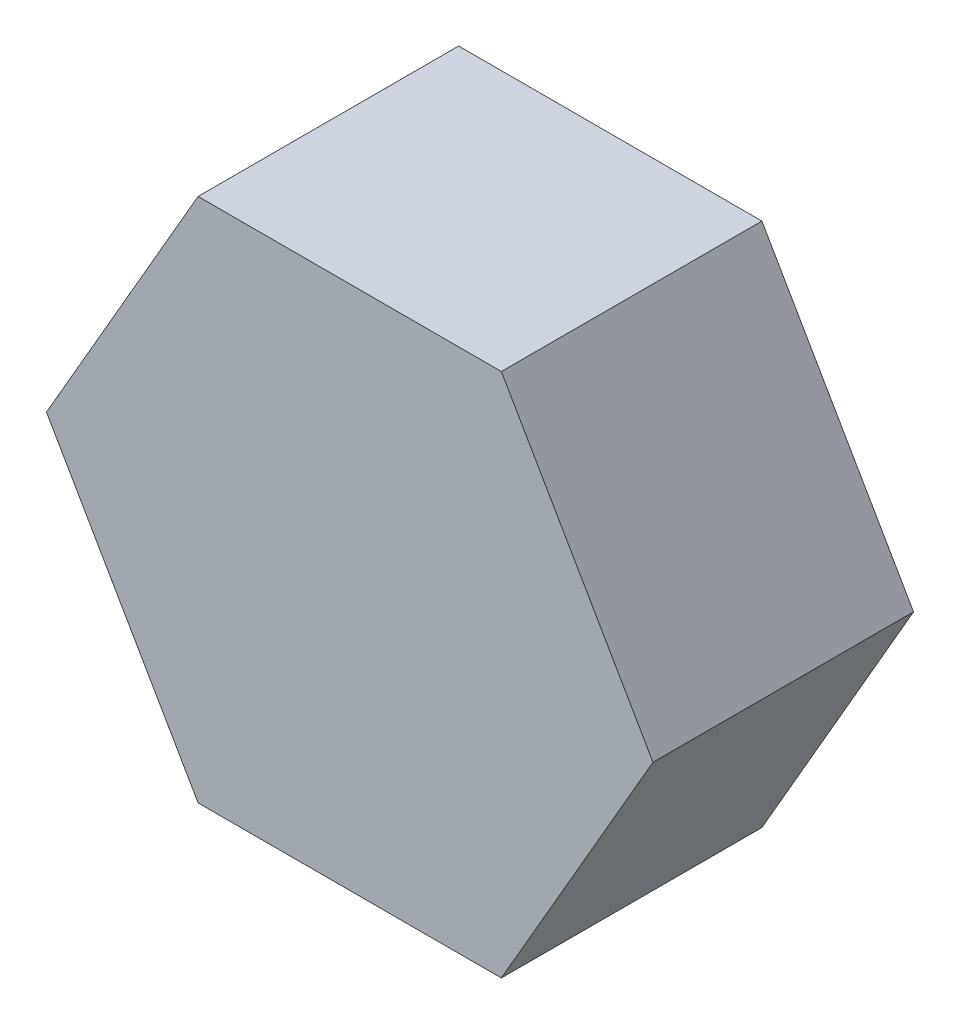
SolidWorks part; units mm, degrees
material "AISI 1020"
ref_plane "Front Plane" through (0, 0, 0) normal (0, 0, 1) x (1, 0, 0)
ref_plane "Top Plane" through (0, 0, 0) normal (0, 1, 0) x (1, 0, 0)
ref_plane "Right Plane" through (0, 0, 0) normal (1, 0, 0) x (0, 0, -1)
sketch "Sketch1" plane through (0, 0, 0) normal (0, 0, 1) x (1, 0, 0)
  line L7 (-14.5492, 25.2) -> (-29.0985, 0)
  line L8 (-29.0985, 0) -> (-14.5492, -25.2)
  line L9 (-14.5492, -25.2) -> (14.5492, -25.2)
  line L10 (14.5492, -25.2) -> (29.0985, 0)
  line L11 (29.0985, 0) -> (14.5492, 25.2)
  line L12 (14.5492, 25.2) -> (-14.5492, 25.2)
  circle A0 centre (0, 0) radius 25.2 construction
  point P10 (0, 25.2)
  dimension "D1" = 50.4
extrude "Boss-Extrude1" add sketch "Sketch1" along normal blind 25
sketch "Sketch2" plane through (0, 0, 0) normal (0, 0, 1) x (1, 0, 0)
  circle A0 centre (0, 0) radius 12.7
  dimension "D1" = 25.4
extrude "Cut-Extrude2" cut sketch "Sketch2" along normal blind 20
thread "Thread1" pitch 2.1167 method cut profile "Thread Profile1" start angle 0, offset 0, length 20, pitch 2.1167, diameter 25.4
ref_plane "Plane1" through (12.7, 0, 0) normal (0, -1, 0) x (1, 0, 0)
sketch "Thread Profile1" plane through (12.7, 0, 0) normal (0, -1, 0) x (1, 0, 0)
  line L0 (0, 0) -> (0, 2.1167) construction
  line L1 (0, 0) -> (1.1457, 0.6615)
  line L2 (1.1457, 0.6615) -> (1.1457, 0.926)
  line L3 (1.1457, 0.926) -> (0, 1.5875)
  line L4 (1.1457, 0.7937) -> (0, 0.7937) construction
  line L11 (0, 0) -> (0, 1.5875)
  point P2 (0, 0)
  dimension "Pitch" = 2.1167
  dimension "Profile_Angle" = 60
  dimension "Profile_Land" = 0.2646
  dimension "Profile_Height" = 1.1457
